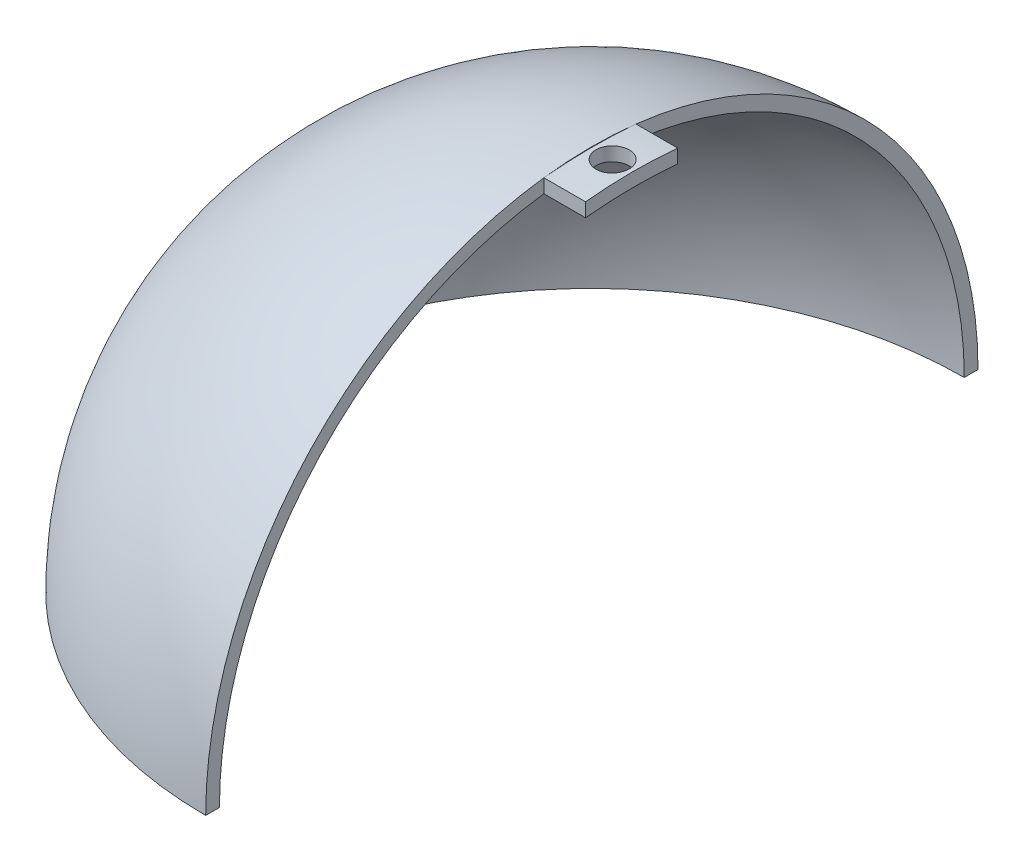
SolidWorks part; units mm, degrees
ref_plane "Front" through (0, 0, 0) normal (0, 0, 1) x (1, 0, 0)
ref_plane "Top" through (0, 0, 0) normal (0, 1, 0) x (1, 0, 0)
ref_plane "Right" through (0, 0, 0) normal (1, 0, 0) x (0, 0, -1)
sketch "Sketch1" plane through (0, 0, 0) normal (0, 1, 0) x (1, 0, 0)
  line L0 (0, 9275) -> (0, 8945)
  line L1 (0, -8945) -> (0, -9275)
  line L3 (0, -41.7154) -> (0, 43.2806) construction
  arc A0 (0, 8945) -> (0, -8945) centre (0, 0) ccw
  arc A1 (0, 9275) -> (0, -9275) centre (0, 0) ccw
  dimension "D1" = 8945
  dimension "D2" = 9275
revolve "Revolve1" add sketch "Sketch1" angle 90 about L3
sketch "Sketch3" plane through (0, 0, 0) normal (1, 0, 0) x (0, 0, -1)
  line L0 (-1151.7595, 9203.21) -> (-1151.7595, 8870.5397)
  line L1 (1061.0832, 8881.8426) -> (1061.0832, 9214.1048)
  arc A0 (-1151.7595, 8870.5397) -> (1061.0832, 8881.8426) centre (12.6156, -2469.8408) cw
  arc A1 (8945, 0) -> (-8945, 0) centre (0, 0) ccw construction
  arc A2 (-1151.7595, 9203.21) -> (1061.0832, 9214.1048) centre (11.5125, -2338.3149) cw
  arc A3 (9275, 0) -> (-9275, 0) centre (0, 0) ccw construction
extrude "Boss-Extrude1" add sketch "Sketch3" along normal blind 1000
sketch "Sketch4" plane through (0, 0, 0) normal (0, 1, 0) x (1, 0, 0)
  line L0 (-5101.25, 0) -> (5101.25, 0) construction
  line L1 (0, -5101.25) -> (0, 5101.25) construction
  circle A0 centre (500, 0) radius 400
  dimension "D1" = 500
extrude "Cut-Extrude1" cut sketch "Sketch4" along normal blind 9275
